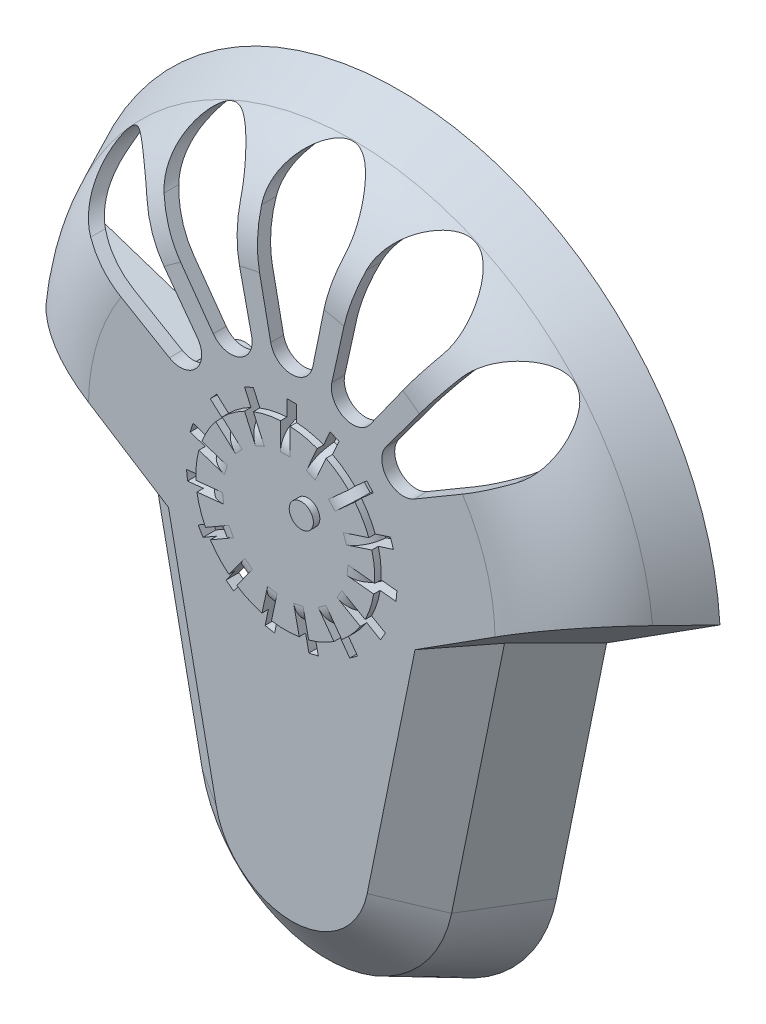
SolidWorks part; units mm, degrees
ref_plane "Front Plane" through (0, 0, 0) normal (0, 0, 1) x (1, 0, 0)
ref_plane "Top Plane" through (0, 0, 0) normal (0, 1, 0) x (1, 0, 0)
ref_plane "Right Plane" through (0, 0, 0) normal (1, 0, 0) x (0, 0, -1)
sketch "Sketch1" plane through (0, 0, 0) normal (0, 0, 1) x (1, 0, 0)
  line L0 (0, 0) -> (0, 61.1104) construction
  line L1 (-18.6676, -3.798) -> (-24.608, 25.4)
  line L2 (-24.608, 25.4) -> (-38.0362, 33.9547)
  line L3 (24.608, 25.4) -> (38.0362, 33.9547)
  line L4 (18.6676, -3.798) -> (24.608, 25.4)
  arc A0 (-18.6676, -3.798) -> (18.6676, -3.798) centre (0, 0) ccw
  arc A2 (-38.0362, 33.9547) -> (38.0362, 33.9547) centre (0, 31.75) cw
  point P11 (0, -10.5863)
  point P12 (0, -10.4087)
  point P13 (4.2699, -9.3057)
  point P14 (0, -1.01)
  dimension "D1" = 38.1
  dimension "D2" = 19.05
  dimension "D3" = 31.75
  dimension "D4" = 23
  dimension "D5" = 115
  dimension "D6" = 25.4
extrude "Boss-Extrude1" add sketch "Sketch1" along normal blind 12.7 draft 25
fillet "Fillet1" radius 12.7 1 edges at (0, 63.9279, 12.7)
chamfer "Chamfer1" distance 4.5974 angle 30 3 edges at (-16.0851, 13.2134, 12.7) (0, -13.1279, 12.7) (16.0851, 13.2134, 12.7) first distance on face at (-18.8614, 12.0072, 6.35) first distance on face at (0, -9.6483, 6.35) first distance on face at (18.8614, 12.0072, 6.35)
shell "Shell1" thickness 1.524 removed face at (0, 21.9595, 0)
sketch "Sketch2" plane through (0, 0, 12.7) normal (0, 0, 1) x (1, 0, 0)
  line L0 (0, 71.1527) -> (0, 0) construction
  line L1 (-2.4887, 49.022) -> (-4.9774, 61.214)
  line L2 (2.4887, 49.022) -> (4.9774, 61.214)
  arc A0 (-4.9774, 61.214) -> (4.9774, 61.214) centre (0, 62.23) cw
  arc A1 (-2.4887, 49.022) -> (2.4887, 49.022) centre (0, 49.53) ccw
  arc A2 (24.0847, 32.0884) -> (-24.0847, 32.0884) centre (0, 31.75) ccw construction
  point P9 (0, 0)
  point P11 (0, 0)
  dimension "D1" = 5.08
  dimension "D2" = 2.54
  dimension "D3" = 12.7
  dimension "D4" = 17.78
extrude "Cut-Extrude1" cut sketch "Sketch2" against normal through all
pattern_circular "CirPattern1" count 3 every 24 about axis through (0, 31.75, 0) along (0, 0, 1) of "Cut-Extrude1" reverse direction yes
mirror "Mirror1" about plane through (0, 0, 0) normal (1, 0, 0) of "CirPattern1"
sketch "Sketch3" plane through (0, 0, 12.7) normal (0, 0, 1) x (1, 0, 0)
  circle A0 centre (0, 31.75) radius 10.6045
  dimension "D1" = 21.209
extrude "Boss-Extrude2" add sketch "Sketch3" along normal blind 0.762
sketch "Sketch4" plane through (0, 0, 13.462) normal (0, 0, 1) x (1, 0, 0)
  line L0 (0, 44.45) -> (0, 0) construction
  line L2 (-0.5718, 44.226) -> (0.5718, 44.226)
  line L3 (-0.5718, 44.226) -> (-0.5718, 41.686)
  line L4 (-0.5718, 41.686) -> (0.5718, 41.686)
  line L5 (0.5718, 44.226) -> (0.5718, 41.686)
  line L6 (-0.5718, 44.226) -> (0.5718, 41.686) construction
  line L7 (-0.5718, 41.686) -> (0.5718, 44.226) construction
  circle A5 centre (0, 31.75) radius 10.6045 construction
  point P3 (0, 42.3545)
  point P8 (0, 22.225)
  dimension "D3" = 9.525
  dimension "D1" = 1.1437
  dimension "D2" = 2.54
extrude "Cut-Extrude2" cut sketch "Sketch4" against normal through all
fillet "Fillet2" radius 2.54 1 edges at (0, 41.686, 13.462)
pattern_circular "CirPattern2" count 15 every 24 about axis through (0, 31.75, 0) along (0, 0, 1) of "Fillet2", "Cut-Extrude2" reverse direction yes
sketch "Sketch5" plane through (0, 0, 13.462) normal (0, 0, 1) x (1, 0, 0)
  circle A0 centre (2.655, 34.6064) radius 1.4325
extrude "Boss-Extrude3" add sketch "Sketch5" along normal blind 0.762
sketch "Sketch6" plane through (0, 0, 11.176) normal (0, 0, -1) x (-1, 0, 0)
  circle A0 centre (0, 31.75) radius 7.62
  circle A1 centre (0, 31.75) radius 6.35
  dimension "D1" = 15.24
  dimension "D2" = 12.7
extrude "Boss-Extrude4" add sketch "Sketch6" along normal blind 2.54
sketch "Sketch7" plane through (0, 0, 11.176) normal (0, 0, -1) x (-1, 0, 0)
  line L0 (0, 0) -> (0, 43.563) construction
  circle A0 centre (0, 0) radius 2.2225
  circle A1 centre (-16.5772, 34.2736) radius 2.2225
  circle A2 centre (16.5772, 34.2736) radius 2.2225
  dimension "D1" = 4.445
extrude "Boss-Extrude5" add sketch "Sketch7" along normal blind 9.525
sketch "Sketch8" plane through (0, 0, 1.651) normal (0, 0, -1) x (-1, 0, 0)
  circle A0 centre (-16.5772, 34.2736) radius 1.3051
  circle A1 centre (16.5772, 34.2736) radius 1.3051
  circle A2 centre (0, 0) radius 1.3051
  dimension "D1" = 2.6101
extrude "Cut-Extrude3" cut sketch "Sketch8" against normal blind 2.54
sketch "Sketch10" plane through (0, 0, 1.651) normal (0, 0, -1) x (-1, 0, 0)
  line L0 (18.7132, 34.8874) -> (33.2777, 39.7079)
  line L1 (0, 0) -> (0, 40.7049) construction
  line L2 (-18.7132, 34.8874) -> (-33.2777, 39.7079)
  line L3 (2.2225, 0) -> (14.1462, 0)
  line L4 (13.5839, -2.7637) -> (19.9633, 28.5922) construction
  line L5 (0, -2.2225) -> (0, -13.8622)
  line L6 (-2.2225, 0) -> (-14.1462, 0)
  line L7 (-19.9633, 28.5922) -> (-13.5839, -2.7637) construction
  arc A1 (33.9559, 35.9605) -> (27.7199, 51.8085) centre (0, 31.75) ccw construction
  circle A2 centre (0, 0) radius 2.2225 construction
  circle A3 centre (0, 0) radius 2.2225 construction
  arc A4 (-13.5839, -2.7637) -> (13.5839, -2.7637) centre (0, 0) ccw construction
  circle A5 centre (16.5772, 34.2736) radius 2.2225 construction
  circle A6 centre (-16.5772, 34.2736) radius 2.2225 construction
  point P2 (18.7132, 34.8874)
  point P31 (-18.7132, 34.8874)
rib "Rib3" sketch "Sketch10" sketch "Sketch10" thickness 1.27 extrusion direction normal to sketch draft on no parameters "D1"=1.27
